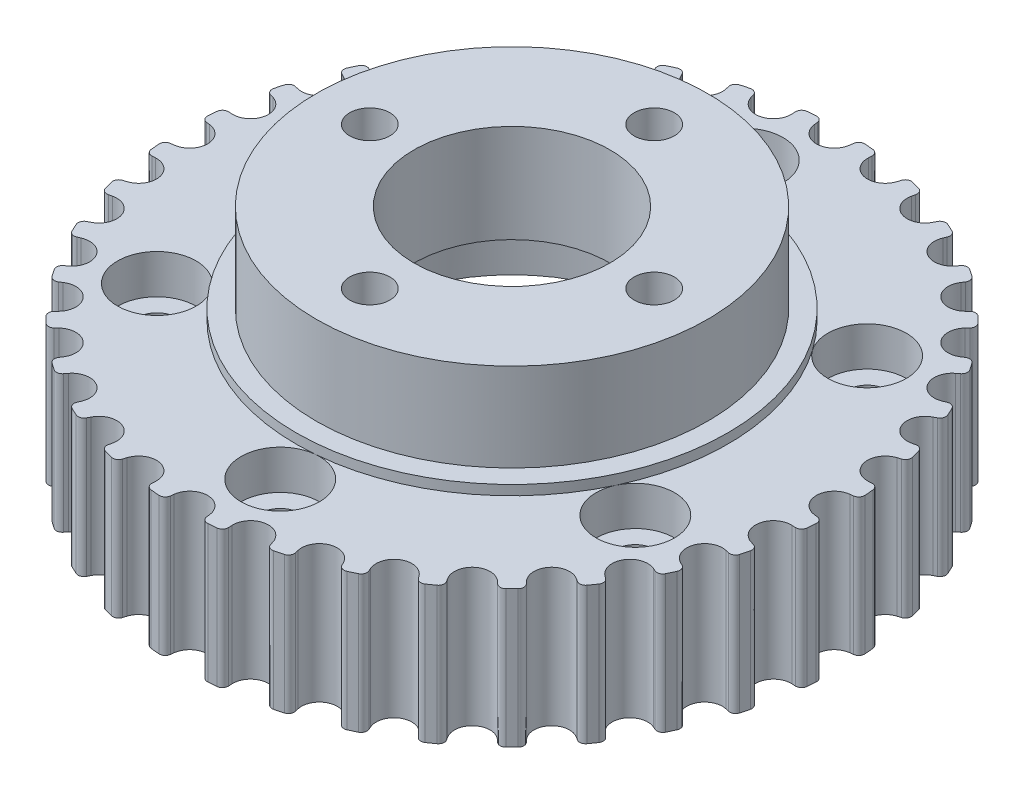
SolidWorks part; units mm, degrees
material "6061 合金"
ref_plane "前视基准面" through (0, 0, 0) normal (0, 0, 1) x (1, 0, 0)
ref_plane "上视基准面" through (0, 0, 0) normal (0, 1, 0) x (1, 0, 0)
ref_plane "右视基准面" through (0, 0, 0) normal (1, 0, 0) x (0, 0, -1)
ref_axis "基准轴1" through (0, -44, 0) along (0, 1, 0)
sketch "草图1" plane through (0, 0, 0) normal (0, 1, 0) x (1, 0, 0)
  circle A0 centre (0, 0) radius 16.8
extrude "凸台-拉伸1" add sketch "草图1" along normal mid plane 7
sketch "草图2" plane through (0, 0, 0) normal (0, 1, 0) x (1, 0, 0)
  line B0 (-0.9032, 16.3191) -> (-0.9244, 16.4912)
  line B1 (0.9032, 16.3191) -> (0.9244, 16.4912)
  arc B2 (-0.9032, 16.3191) -> (0.9032, 16.3191) centre (0, 16.43) ccw
  arc B3 (-1.2443, 16.7539) -> (1.2443, 16.7539) centre (0, 0) cw
  arc B4 (-0.9244, 16.4912) -> (-1.2443, 16.7539) centre (-1.2221, 16.4547) ccw
  arc B5 (1.2443, 16.7539) -> (0.9244, 16.4912) centre (1.2221, 16.4547) ccw
sketch_block_instance "HTD-1"
sketch_block "HTD" parameters "OD"=33.6, "D4"=0.3, "Rb"=0.91, "Rt"=0.3, "Dh"=1.28, "deg"=14
extrude "切除-拉伸1" cut sketch "草图2" against normal mid plane 100
pattern_circular "阵列(圆周)1" count 36 over 360 about axis through (0, -44, 0) along (0, 1, 0) of "切除-拉伸1"
sketch "草图4" plane through (0, 0, 0) normal (0, 1, 0) x (1, 0, 0)
  circle A0 centre (0, 0) radius 7.75
  dimension "D1" = 15.5
extrude "切除-拉伸2" cut sketch "草图4" against normal mid plane 100
sketch "草图6" plane through (0, -3.5, 0) normal (0, 1, 0) x (1, 0, 0)
  circle A0 centre (0, 0) radius 18
  dimension "D1" = 36
sketch "草图8" plane through (0, 3.5, 0) normal (0, 1, 0) x (1, 0, 0)
  circle A0 centre (0, 0) radius 9.5 construction
  circle A1 centre (0, 9.5) radius 1.5
  circle A2 centre (8.2272, -4.75) radius 1.5
  circle A3 centre (-8.2272, -4.75) radius 1.5
  point P11 (0, 0)
  dimension "D1" = 3
  dimension "D2" = 19
  dimension "D3" = 3
sketch "草图10" plane through (0, 3.5, 0) normal (0, 1, 0) x (1, 0, 0)
  line L0 (5.7941, 8.0745) -> (7.5231, 10.5438)
  line L1 (0, 0) -> (19.7627, 0) construction
  line L2 (9.8834, 1.0122) -> (12.8872, 1.275)
  line L3 (4.0957, -9.0551) -> (5.3697, -11.7872)
  line L4 (-4.0651, -9.0654) -> (-5.3394, -11.7982)
  line L5 (-9.8898, 0.9806) -> (-12.8928, 1.2433)
  line L6 (-5.8183, 8.0532) -> (-7.5478, 10.5231)
  arc A0 (13.7847, 2.4459) -> (8.984, 10.7372) centre (0, 0) ccw
  arc A1 (8.8166, 1.8076) -> (5.952, 6.7509) centre (0, 0) ccw
  arc A2 (5.952, 6.7509) -> (5.7941, 8.0745) centre (6.6133, 7.501) cw
  arc A3 (9.8834, 1.0122) -> (8.8166, 1.8076) centre (9.7962, 2.0084) cw
  arc A4 (12.8872, 1.275) -> (13.7847, 2.4459) centre (12.8001, 2.2712) ccw
  arc A5 (8.984, 10.7372) -> (7.5231, 10.5438) centre (8.3423, 9.9703) ccw
  arc A6 (-4.7741, -13.1608) -> (4.8067, -13.149) centre (0, 0) ccw
  arc A7 (-2.8429, -8.5392) -> (2.8705, -8.53) centre (0, 0) ccw
  arc A8 (2.8705, -8.53) -> (4.0957, -9.0551) centre (3.1894, -9.4778) cw
  arc A9 (-5.3394, -11.7982) -> (-4.7741, -13.1608) centre (-4.4331, -12.2208) ccw
  arc A10 (4.8067, -13.149) -> (5.3697, -11.7872) centre (4.4634, -12.2098) ccw
  arc A11 (-4.0651, -9.0654) -> (-2.8429, -8.5392) centre (-3.1588, -9.488) cw
  arc A12 (-9.0106, 10.7149) -> (-13.7907, 2.4118) centre (0, 0) ccw
  arc A13 (-5.9737, 6.7316) -> (-8.8224, 1.7791) centre (0, 0) ccw
  arc A14 (-8.8224, 1.7791) -> (-9.8898, 0.9806) centre (-9.8027, 1.9768) cw
  arc A15 (-7.5478, 10.5231) -> (-9.0106, 10.7149) centre (-8.367, 9.9496) ccw
  arc A16 (-13.7907, 2.4118) -> (-12.8928, 1.2433) centre (-12.8056, 2.2395) ccw
  arc A17 (-5.8183, 8.0532) -> (-5.9737, 6.7316) centre (-6.6375, 7.4796) cw
  point P41 (0, 0)
  dimension "D1" = 28
  dimension "D2" = 18
  dimension "D3" = 5
  dimension "D5" = 1
  dimension "D4" = 55
  dimension "D6" = 3
sketch "草图11" plane through (0, -3.5, 0) normal (0, -1, 0) x (1, 0, 0)
  circle A0 centre (0, 0) radius 9
  dimension "D1" = 18
extrude "切除-拉伸9" cut sketch "草图11" against normal blind 3.5
sketch "草图14" plane through (0, 3.5, 0) normal (0, 1, 0) x (1, 0, 0)
  circle A0 centre (0, 0) radius 9.975
  circle A1 centre (0, 0) radius 5
  dimension "D1" = 19.95
  dimension "D2" = 10
extrude "凸台-拉伸3" add sketch "草图14" along normal blind 5
sketch "草图15" plane through (0, 8.5, 0) normal (0, 1, 0) x (1, 0, 0)
  circle A0 centre (0, 0) radius 7.25 construction
  circle A1 centre (0, 7.25) radius 1.025
  circle A2 centre (7.25, 0) radius 1.025
  circle A3 centre (0, -7.25) radius 1.025
  circle A4 centre (-7.25, 0) radius 1.025
  point P14 (0, 0)
  dimension "D1" = 14.5
  dimension "D2" = 2.05
  dimension "D3" = 4
extrude "切除-拉伸10" cut sketch "草图15" against normal blind 4
sketch "草图16" plane through (0, -3.5, 0) normal (0, -1, 0) x (1, 0, 0)
  circle A0 centre (0, 0) radius 14.5
  dimension "D2" = 29
extrude "切除-拉伸12" cut sketch "草图16" against normal blind 3.5
sketch "草图17" plane through (0, 3.5, 0) normal (0, 1, 0) x (1, 0, 0)
  line L0 (0, 0) -> (-1.4642, 16.7361) construction
  circle A0 centre (0, 0) radius 13 construction
  circle A1 centre (-1.133, 12.9505) radius 1
  circle A7 centre (10.649, 7.4565) radius 1
  circle A13 centre (11.782, -5.494) radius 1
  circle A14 centre (1.133, -12.9505) radius 1
  circle A15 centre (-10.649, -7.4565) radius 1
  circle A16 centre (-11.782, 5.494) radius 1
  point P19 (0, 0)
  dimension "D1" = 26
  dimension "D2" = 2
  dimension "D3" = 6
extrude "切除-拉伸13" cut sketch "草图17" against normal blind 10
sketch "草图20" plane through (0, 3.5, 0) normal (0, 1, 0) x (1, 0, 0)
  circle A1 centre (-11.782, 5.494) radius 2
  circle A2 centre (-1.133, 12.9505) radius 2
  circle A3 centre (10.649, 7.4565) radius 2
  circle A4 centre (11.782, -5.494) radius 2
  circle A5 centre (1.133, -12.9505) radius 2
  circle A6 centre (-10.649, -7.4565) radius 2
  point P16 (0, 0)
  dimension "D1" = 4
  dimension "D2" = 6
extrude "切除-拉伸15" cut sketch "草图20" against normal blind 2
sketch "草图21" plane through (0, 3.5, 0) normal (0, 1, 0) x (1, 0, 0)
  circle A0 centre (0, 0) radius 11
  circle A1 centre (0, 0) radius 9.975
  dimension "D1" = 22
extrude "凸台-拉伸4" add sketch "草图21" along normal blind 0.5
